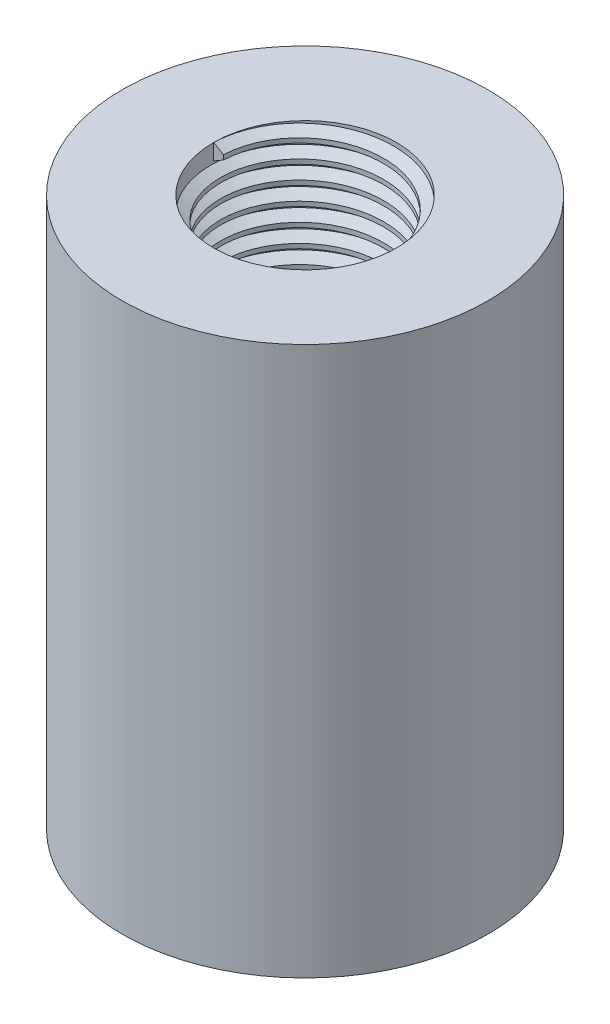
SolidWorks part; units mm, degrees
ref_plane "Front Plane" through (0, 0, 0) normal (0, 0, 1) x (1, 0, 0)
ref_plane "Top Plane" through (0, 0, 0) normal (0, 1, 0) x (1, 0, 0)
ref_plane "Right Plane" through (0, 0, 0) normal (1, 0, 0) x (0, 0, -1)
sketch "Sketch1" plane through (0, 0, 0) normal (0, 1, 0) x (1, 0, 0)
  circle A0 centre (0, 0) radius 12.7
  circle A1 centre (0, 0) radius 6.35
  dimension "D1" = 25.4
  dimension "D2" = 12.7
extrude "Boss-Extrude1" add sketch "Sketch1" along normal blind 38.1
thread "Thread1" pitch 1.27 method extrude profile "Thread Profile1" start angle 0, offset 0, length 38.1, pitch 1.27, diameter 12.7
ref_plane "Plane1" through (-6.35, 38.1, 0) normal (0, 0, 1) x (-1, 0, 0)
sketch "Thread Profile1" plane through (-6.35, 38.1, 0) normal (0, 0, 1) x (-1, 0, 0)
  line L0 (0, 0) -> (0, 1.27) construction
  line L11 (0, 0) -> (0, 1.1112)
  line L12 (0, 1.1112) -> (-0.6874, 0.7144)
  line L13 (-0.6874, 0.7144) -> (-0.6874, 0.3969)
  line L15 (-0.6874, 0.3969) -> (0, 0)
  line L17 (-0.6874, 0.5556) -> (0, 0.5556) construction
  point P2 (0, 0)
  dimension "Pitch" = 1.27
  dimension "Profile_Angle" = 60
  dimension "Profile_Land" = 0.3175
  dimension "Profile_Height" = 0.6874
